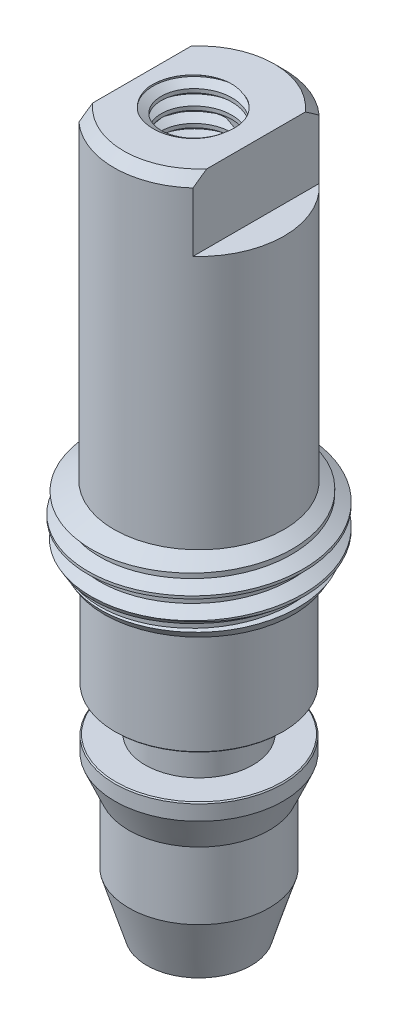
SolidWorks part; units mm, degrees
material "1023 Carbon Steel Sheet (SS)"
ref_plane "Front Plane" through (0, 0, 0) normal (0, 0, 1) x (1, 0, 0)
ref_plane "Top Plane" through (0, 0, 0) normal (0, 1, 0) x (1, 0, 0)
ref_plane "Right Plane" through (0, 0, 0) normal (1, 0, 0) x (0, 0, -1)
sketch "Sketch2" plane through (0, 0, 0) normal (0, 1, 0) x (1, 0, 0)
  circle A0 centre (0, 0) radius 5
  dimension "D1" = 10
extrude "Boss-Extrude1" add sketch "Sketch2" along normal blind 3.2
sketch "Sketch3" plane through (0, 3.2, 0) normal (0, 1, 0) x (1, 0, 0)
  circle A0 centre (0, 0) radius 3.95
  dimension "D1" = 7.9
extrude "Boss-Extrude2" add sketch "Sketch3" along normal blind 15
sketch "Sketch4" plane through (0, 18.2, 0) normal (0, 1, 0) x (1, 0, 0)
  line L1 (-2.65, 6.5) -> (2.65, 6.5)
  line L2 (-2.65, 6.5) -> (-2.65, -6.5)
  line L3 (-2.65, -6.5) -> (2.65, -6.5)
  line L4 (2.65, 6.5) -> (2.65, -6.5)
  dimension "D1" = 5.3
  dimension "D2" = 2.65
  dimension "D3" = 13
  dimension "D4" = 6.5
extrude "Cut-Extrude1" cut sketch "Sketch4" against normal blind 3.2 flip side to cut
sketch "Sketch5" plane through (0, 18.2, 0) normal (0, 1, 0) x (1, 0, 0)
  circle A0 centre (0, 0) radius 3.5
  dimension "D1" = 7
extrude "Cut-Extrude2" cut sketch "Sketch5" against normal blind 10 draft 45 flip side to cut
sketch "Sketch7" plane through (0, 0, 0) normal (0, -1, 0) x (1, 0, 0)
  circle A0 centre (0, 0) radius 3.91
  dimension "D1" = 7.82
extrude "Boss-Extrude3" add sketch "Sketch7" along normal blind 5
sketch "Sketch8" plane through (0, -5, 0) normal (0, -1, 0) x (1, 0, 0)
  circle A0 centre (0, 0) radius 2.5
  dimension "D1" = 5
extrude "Boss-Extrude4" add sketch "Sketch8" along normal blind 2
sketch "Sketch9" plane through (0, -7, 0) normal (0, -1, 0) x (1, 0, 0)
  circle A0 centre (0, 0) radius 3.91
  dimension "D1" = 7.82
extrude "Boss-Extrude5" add sketch "Sketch9" along normal blind 2.25
sketch "Sketch10" plane through (0, -9.25, 0) normal (0, -1, 0) x (1, 0, 0)
  circle A0 centre (0, 0) radius 3.26
  dimension "D1" = 6.52
extrude "Boss-Extrude6" add sketch "Sketch10" along normal blind 5.85
chamfer "Chamfer1" distance 0.05 1 edges at (0, -5, -3.91)
chamfer "Chamfer2" distance 0.05 angle 45 1 edges at (0, -7, -3.91)
chamfer "Chamfer3" distance 1.5 angle 23.5 1 edges at (0, -9.25, -3.91)
sketch "Sketch12" plane through (0, -15.1, 0) normal (0, -1, 0) x (1, 0, 0)
  circle A0 centre (0, 0) radius 2.425
  dimension "D1" = 4.85
extrude "Cut-Extrude3" cut sketch "Sketch12" against normal blind 5.85 draft 17 flip side to cut
chamfer "Chamfer4" distance 1.05 angle 30 2 edges at (0, 3.2, 5) (0, 0, 5)
thread "Thread1" pitch 1 start angle 0, offset 3, length 0, pitch 1, diameter 10
ref_plane "Plane1" through (-5, 5.5938, 0) normal (0, 0, 1) x (-1, 0, 0)
sketch "Thread Profile1" plane through (-5, 5.5938, 0) normal (0, 0, 1) x (-1, 0, 0)
  line L0 (0, 0) -> (0, 1) construction
  line L11 (0, 0) -> (0, 0.875)
  line L12 (0, 0.875) -> (-0.5413, 0.5625)
  line L13 (-0.5413, 0.5625) -> (-0.5413, 0.3125)
  line L15 (-0.5413, 0.3125) -> (0, 0)
  line L17 (-0.5413, 0.4375) -> (0, 0.4375) construction
  point P2 (0, 0)
  dimension "Pitch" = 1
  dimension "Profile_Angle" = 60
  dimension "Profile_Land" = 0.25
  dimension "Profile_Height" = 0.5413
sketch "Sketch22" plane through (0, 18.2, 0) normal (0, 1, 0) x (1, 0, 0)
  point P0 (0, 0)
hole_wizard "Tap Drill for M4x0.7 Tap2" positions "Sketch22" profile "Sketch21" hole size "M4x0.7" standard "ANSI Metric"
sketch "Sketch21" plane through (0, 18.2, 0) normal (1, 0, 0) x (0, 0, 1)
  line L0 (0, 0) -> (0, 15)
  line L1 (0, 15) -> (1.65, 14.0086)
  line L2 (1.65, 14.0086) -> (1.65, 0)
  line L5 (1.65, 0) -> (0, 0)
  line L10 (0, 15) -> (-1.65, 14.0086) construction
  line L11 (0, -6.35) -> (0, 107.95) construction
  dimension "Hole Dia." = 3.3
  dimension "Hole Depth" = 15
  dimension "Drill Angle" = 118
thread "Thread2" pitch 0.7 profile "Thread Profile2" start angle 0, offset 3, length 0, pitch 0.7, diameter 3.3
ref_plane "Plane2" through (-1.65, 21.2, 0) normal (0, 0, 1) x (-1, 0, 0)
sketch "Thread Profile2" plane through (-1.65, 21.2, 0) normal (0, 0, 1) x (-1, 0, 0)
  line L0 (0, 0) -> (0, 0.7) construction
  line L1 (0, 0) -> (0.3789, 0.2187)
  line L2 (0.3789, 0.2187) -> (0.3789, 0.3062)
  line L3 (0.3789, 0.3062) -> (0, 0.525)
  line L4 (0.3789, 0.2625) -> (0, 0.2625) construction
  line L11 (0, 0) -> (0, 0.525)
  point P2 (0, 0)
  dimension "Pitch" = 0.7
  dimension "Profile_Angle" = 60
  dimension "Profile_Land" = 0.0875
  dimension "Profile_Height" = 0.3789
